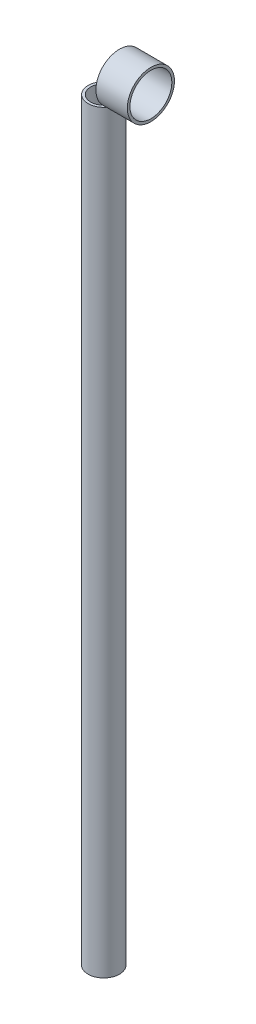
SolidWorks part; units mm, degrees
ref_plane "Front Plane" through (0, 0, 0) normal (0, 0, 1) x (1, 0, 0)
ref_plane "Top Plane" through (0, 0, 0) normal (0, 1, 0) x (1, 0, 0)
ref_plane "Right Plane" through (0, 0, 0) normal (1, 0, 0) x (0, 0, -1)
sketch "Sketch1" plane through (0, 0, 0) normal (0, 1, 0) x (1, 0, 0)
  circle A0 centre (0, 0) radius 19.05
  circle A1 centre (0, 0) radius 15.875
  dimension "D1" = 3.175
  dimension "D2" = 38.1
extrude "Boss-Extrude1" add sketch "Sketch1" along normal blind 914.4
sketch "Sketch2" plane through (0, 0, 0) normal (1, 0, 0) x (0, 0, -1)
  line L1 (19.05, 914.4) -> (-19.05, 914.4) construction
  circle A0 centre (0, 942.975) radius 28.575
  circle A1 centre (0, 942.975) radius 25.4
  point P2 (-29.3704, 939.7445)
  point P6 (0, 0)
  dimension "D1" = 57.15
  dimension "D2" = 3.175
extrude "Boss-Extrude2" add sketch "Sketch2" along normal blind 57.15 separate body
sketch "Sketch3" plane through (0, 0, 0) normal (-1, 0, 0) x (0, 0, 1)
  circle A0 centre (0, 942.975) radius 28.575
  circle A1 centre (0, 942.975) radius 25.4
  circle A2 centre (0, 942.975) radius 28.575 construction
  circle A3 centre (0, 942.975) radius 25.4 construction
extrude "Cut-Extrude1" cut sketch "Sketch3" against normal blind 19.05
